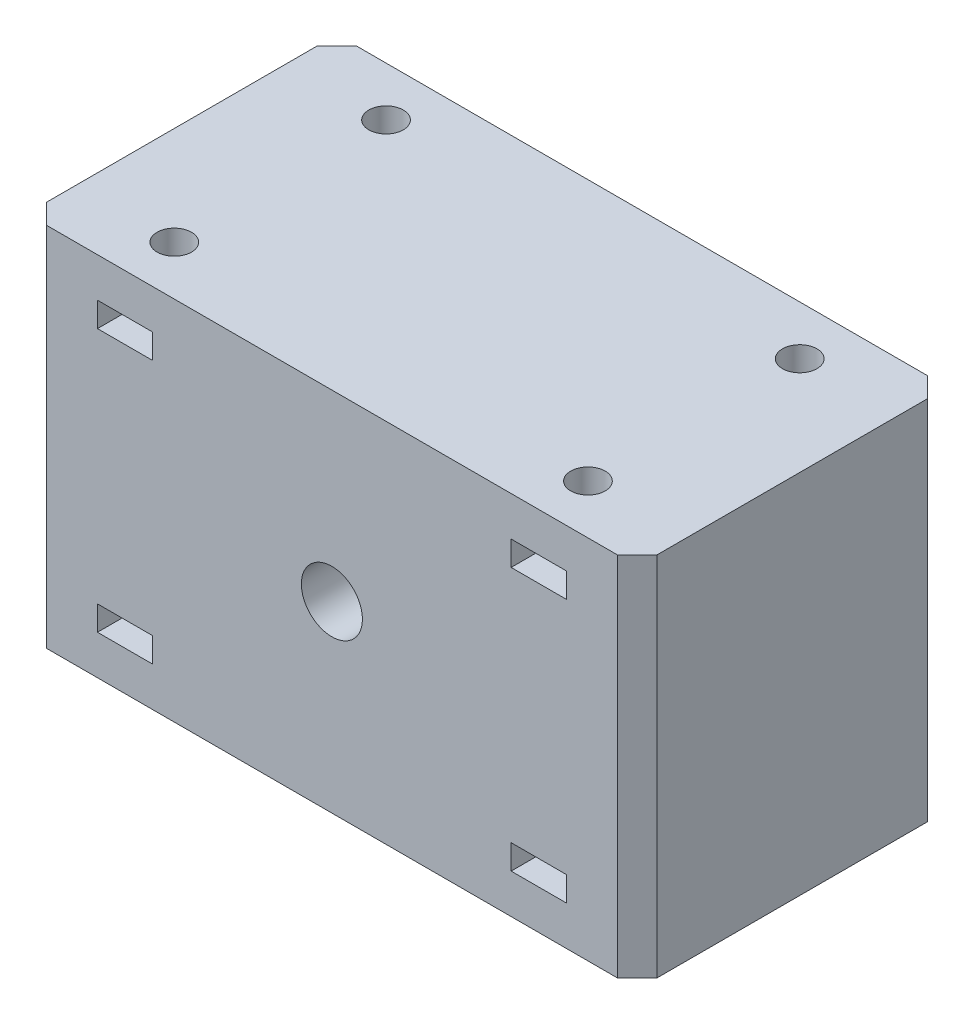
SolidWorks part; units mm, degrees
ref_plane "Front Plane" through (0, 0, 0) normal (0, 0, 1) x (1, 0, 0)
ref_plane "Top Plane" through (0, 0, 0) normal (0, 1, 0) x (1, 0, 0)
ref_plane "Right Plane" through (0, 0, 0) normal (1, 0, 0) x (0, 0, -1)
ref_plane "Plane1" through (0, -18.6, 0) normal (0, 1, 0) x (1, 0, 0)
ref_plane "Plane2" through (0, 18.6, 0) normal (0, 1, 0) x (1, 0, 0)
sketch "Sketch1" plane through (0, 18.6, 0) normal (0, 1, 0) x (1, 0, 0)
  line L0 (32, -7) -> (32, 7) construction
  line L1 (32, -7) -> (32, 7)
  line L2 (-32, 7) -> (-32, -7) construction
  line L3 (-32, 7) -> (-32, -7)
ref_plane "Plane3" through (0, 0, 15.75) normal (0, 0, 1) x (1, 0, 0)
ref_plane "Plane4" through (0, 0, -15.75) normal (0, 0, 1) x (1, 0, 0)
sketch "Sketch2" plane through (0, 0, 0) normal (0, 1, 0) x (1, 0, 0)
  line L0 (-32, 7) -> (-32, -7) construction
  line L1 (32, -7) -> (32, 7) construction
  line L2 (-32, 7) -> (-32, -7) construction
  line L3 (32, -7) -> (32, 7) construction
  line L4 (-55, 15.75) -> (55, 15.75) construction
  line L5 (-31, 15.75) -> (31, 15.75)
  line L6 (-31, 15.75) -> (-31, -15.75)
  line L7 (-31, -15.75) -> (31, -15.75)
  line L8 (31, 15.75) -> (31, -15.75)
  line L9 (-55, -15.75) -> (55, -15.75) construction
  point P12 (0, 15.75)
  dimension "D1" = 1
extrude "Boss-Extrude1" add sketch "Sketch2" along normal up to surface (18.6 mm away) and the other way up to surface (18.6 mm away) up to plane "Plane2" other way up to plane "Plane1"
sketch "Sketch3" plane through (0, 0, 0) normal (0, 0, 1) x (1, 0, 0)
  circle A0 centre (0, 0) radius 3.1
  dimension "D1" = 6.2
extrude "Cut-Extrude1" cut sketch "Sketch3" against normal through all and the other way through all
sketch "Sketch4" plane through (0, 0, 0) normal (0, 1, 0) x (1, 0, 0)
  line L1 (-21, -10.75) -> (21, -10.75) construction
  line L2 (-21, -10.75) -> (-21, 10.75) construction
  line L3 (-21, 10.75) -> (21, 10.75) construction
  line L4 (31, 15.75) -> (-31, 15.75)
  line L5 (31, -15.75) -> (31, 15.75)
  line L6 (-31, -15.75) -> (31, -15.75)
  line L7 (-31, 15.75) -> (-31, -15.75)
  line L8 (31, 15.75) -> (-31, 15.75) construction
  line L9 (31, -15.75) -> (31, 15.75) construction
  line L10 (-31, -15.75) -> (31, -15.75) construction
  line L11 (-31, 15.75) -> (-31, -15.75) construction
  line L12 (21, -10.75) -> (21, 10.75) construction
  line L13 (-21, -10.75) -> (21, 10.75) construction
  line L14 (-21, 10.75) -> (21, -10.75) construction
  circle A0 centre (-21, 10.75) radius 1.75
  circle A1 centre (21, 10.75) radius 1.75
  circle A2 centre (21, -10.75) radius 1.75
  circle A3 centre (-21, -10.75) radius 1.75
  point P2 (0, 0)
  dimension "D2" = 3.5
  dimension "D3" = 10
  dimension "D4" = 5
  dimension "D1" = 0
sketch "Sketch5" plane through (0, 18.6, 0) normal (0, 1, 0) x (1, 0, 0)
  circle A1 centre (-21, -10.75) radius 1.75
  circle A2 centre (-21, -10.75) radius 1.75
  circle A3 centre (21, -10.75) radius 1.75
  circle A4 centre (21, -10.75) radius 1.75
  circle A5 centre (21, 10.75) radius 1.75
  circle A6 centre (21, 10.75) radius 1.75
  circle A7 centre (-21, 10.75) radius 1.75
  circle A8 centre (-21, 10.75) radius 1.75
  dimension "D1" = 0
  dimension "D2" = 0
  dimension "D3" = 0
  dimension "D4" = 0
extrude "Cut-Extrude2" cut sketch "Sketch5" against normal blind 10
sketch "Sketch6" plane through (0, -18.6, 0) normal (0, -1, 0) x (1, 0, 0)
  circle A1 centre (-21, 10.75) radius 1.75
  circle A2 centre (-21, 10.75) radius 1.75
  circle A3 centre (21, 10.75) radius 1.75
  circle A4 centre (21, 10.75) radius 1.75
  circle A5 centre (21, -10.75) radius 1.75
  circle A6 centre (21, -10.75) radius 1.75
  circle A7 centre (-21, -10.75) radius 1.75
  circle A8 centre (-21, -10.75) radius 1.75
  dimension "D1" = 0
  dimension "D2" = 0
  dimension "D3" = 0
  dimension "D4" = 0
extrude "Cut-Extrude3" cut sketch "Sketch6" against normal blind 10
sketch "Sketch7" plane through (0, 18.6, 0) normal (0, 1, 0) x (1, 0, 0)
  line L0 (-21, 15.75) -> (-21, -15.75) construction
  line L1 (31, 15.75) -> (-31, 15.75) construction
  line L2 (-31, -15.75) -> (31, -15.75) construction
  line L3 (21, 15.75) -> (21, -15.75) construction
  line L4 (-21, -10.75) -> (-21, 10.75) construction
  line L5 (21, -10.75) -> (21, 10.75) construction
  line L6 (31, 15.75) -> (-31, 15.75) construction
  line L7 (-23.8, 15.75) -> (-18.2, 15.75)
  line L8 (-23.8, 15.75) -> (-23.8, 7.4)
  line L9 (-23.8, 7.4) -> (-18.2, 7.4)
  line L10 (-18.2, 15.75) -> (-18.2, 7.4)
  line L11 (-21, 0) -> (21, 0) construction
  line L12 (0, 10.75) -> (0, -10.75) construction
  line L13 (-21, 10.75) -> (21, 10.75) construction
  line L14 (-21, -10.75) -> (21, -10.75) construction
  line L15 (0, -17.325) -> (0, 17.325) construction
  line L16 (23.8, 7.4) -> (18.2, 7.4)
  line L17 (18.2, 15.75) -> (18.2, 7.4)
  line L18 (23.8, 15.75) -> (18.2, 15.75)
  line L19 (23.8, 15.75) -> (23.8, 7.4)
  line L20 (-20.46, 0) -> (20.46, 0) construction
  line L21 (23.8, -15.75) -> (23.8, -7.4)
  line L22 (23.8, -15.75) -> (18.2, -15.75)
  line L23 (18.2, -15.75) -> (18.2, -7.4)
  line L24 (23.8, -7.4) -> (18.2, -7.4)
  line L25 (-23.8, -7.4) -> (-18.2, -7.4)
  line L26 (-18.2, -15.75) -> (-18.2, -7.4)
  line L27 (-23.8, -15.75) -> (-18.2, -15.75)
  line L28 (-23.8, -15.75) -> (-23.8, -7.4)
  circle A0 centre (-21, 10.75) radius 1.75 construction
  point P19 (-21, 7.4)
  point P20 (-21, 9)
  dimension "D1" = 5.6
  dimension "D2" = 1.6
extrude "Cut-Extrude4" cut sketch "Sketch7" against normal blind 2.5 from offset 4 offset against normal yes
sketch "Sketch8" plane through (0, -18.6, 0) normal (0, -1, 0) x (1, 0, 0)
  line L4 (-23.8, -15.75) -> (-18.2, -15.75)
  line L5 (-18.2, -15.75) -> (-18.2, -7.4)
  line L6 (-18.2, -7.4) -> (-23.8, -7.4)
  line L7 (-23.8, -7.4) -> (-23.8, -15.75)
  line L8 (-23.8, -15.75) -> (-18.2, -15.75)
  line L9 (-18.2, -15.75) -> (-18.2, -7.4)
  line L10 (-18.2, -7.4) -> (-23.8, -7.4)
  line L11 (-23.8, -7.4) -> (-23.8, -15.75)
  line L12 (-23.8, 7.4) -> (-18.2, 7.4)
  line L13 (-18.2, 7.4) -> (-18.2, 15.75)
  line L14 (-18.2, 15.75) -> (-23.8, 15.75)
  line L15 (-23.8, 15.75) -> (-23.8, 7.4)
  line L16 (-23.8, 7.4) -> (-18.2, 7.4)
  line L17 (-18.2, 7.4) -> (-18.2, 15.75)
  line L18 (-18.2, 15.75) -> (-23.8, 15.75)
  line L19 (-23.8, 15.75) -> (-23.8, 7.4)
  line L20 (23.8, 7.4) -> (23.8, 15.75)
  line L21 (18.2, 7.4) -> (23.8, 7.4)
  line L22 (18.2, 15.75) -> (18.2, 7.4)
  line L23 (23.8, 15.75) -> (18.2, 15.75)
  line L24 (23.8, 7.4) -> (23.8, 15.75)
  line L25 (18.2, 7.4) -> (23.8, 7.4)
  line L26 (18.2, 15.75) -> (18.2, 7.4)
  line L27 (23.8, 15.75) -> (18.2, 15.75)
  line L28 (23.8, -7.4) -> (18.2, -7.4)
  line L29 (18.2, -7.4) -> (18.2, -15.75)
  line L30 (18.2, -15.75) -> (23.8, -15.75)
  line L31 (23.8, -15.75) -> (23.8, -7.4)
  line L32 (23.8, -7.4) -> (18.2, -7.4)
  line L33 (18.2, -7.4) -> (18.2, -15.75)
  line L34 (18.2, -15.75) -> (23.8, -15.75)
  line L35 (23.8, -15.75) -> (23.8, -7.4)
  dimension "D1" = 0
  dimension "D2" = 0
  dimension "D3" = 0
  dimension "D4" = 0
extrude "Cut-Extrude5" cut sketch "Sketch8" against normal blind 2.5 from offset 4 offset against normal yes
chamfer "Chamfer1" distance 2 angle 45 4 edges at (-31, 0, -15.75) (31, 0, -15.75) (-31, 0, 15.75) (31, 0, 15.75)
